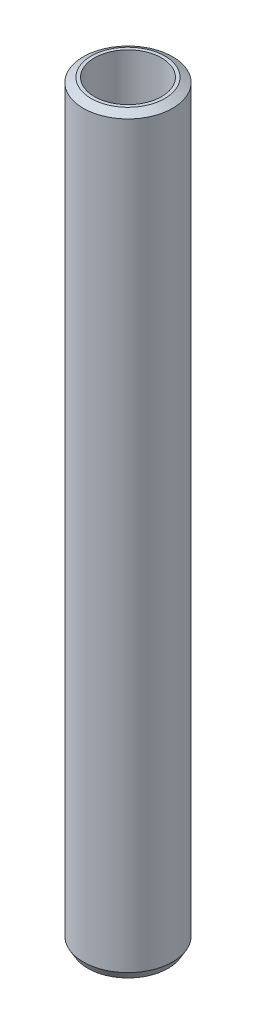
SolidWorks part; units mm, degrees
ref_plane "Front Plane" through (0, 0, 0) normal (0, 0, 1) x (1, 0, 0)
ref_plane "Top Plane" through (0, 0, 0) normal (0, 1, 0) x (1, 0, 0)
ref_plane "Right Plane" through (0, 0, 0) normal (1, 0, 0) x (0, 0, -1)
sketch "Sketch1" plane through (0, 0, 0) normal (0, 1, 0) x (1, 0, 0)
  circle A0 centre (0, 0) radius 35
  dimension "SHAFT_OD" = 70
extrude "Boss-Extrude1" add sketch "Sketch1" along normal blind 588.7457
sketch "Sketch2" plane through (0, 0, 0) normal (0, 1, 0) x (1, 0, 0)
  circle A0 centre (0, 0) radius 26.3053
  dimension "BORE_D" = 52.6106
extrude "Cut-Extrude1" cut sketch "Sketch2" along normal through all
chamfer "Chamfer1" distance 3.5516 angle 60 2 edges at (0, 588.7457, 35) (0, 0, 35) first distance on face at (0, 588.7457, 35) first distance on face at (0, 0, 26.3053)
